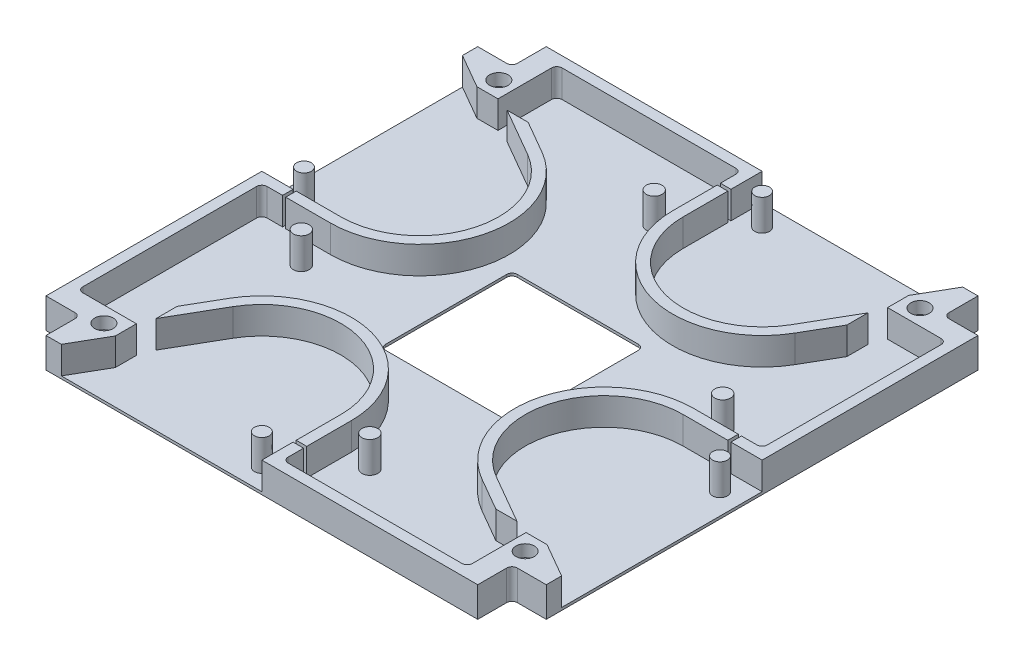
SolidWorks part; units mm, degrees
material "7075-T6 (SN)"
ref_plane "Front Plane" through (0, 0, 0) normal (0, 0, 1) x (1, 0, 0)
ref_plane "Top Plane" through (0, 0, 0) normal (0, 1, 0) x (1, 0, 0)
ref_plane "Right Plane" through (0, 0, 0) normal (1, 0, 0) x (0, 0, -1)
sketch "Sketch1" plane through (0, 0, 0) normal (0, 1, 0) x (1, 0, 0)
  line L0 (0, 0) -> (0, 6.51)
  line L21 (0, 6.51) -> (82, 6.51)
  line L22 (82, 6.51) -> (82, 0)
  line L23 (82, 0) -> (88.51, 0)
  line L24 (88.51, 0) -> (88.51, -82)
  line L25 (88.51, -82) -> (82, -82)
  line L26 (82, -82) -> (82, -88.51)
  line L27 (82, -88.51) -> (0, -88.51)
  line L28 (0, -88.51) -> (0, -82)
  line L29 (0, -82) -> (-6.51, -82)
  line L30 (-6.51, -82) -> (-6.51, 0)
  line L31 (-6.51, 0) -> (0, 0)
  dimension "D1" = 82
  dimension "D2" = 6.51
extrude "Boss-Extrude1" add sketch "Sketch1" along normal blind 0.5
sketch "Sketch2" plane through (0, 0.5, 0) normal (0, 1, 0) x (1, 0, 0)
  line L0 (-6.51, 0) -> (-6.51, -82) construction
  line L1 (0, 6.51) -> (41, 6.51)
  line L2 (0, 6.51) -> (0, 4.51)
  line L3 (0, 4.51) -> (41, 4.51)
  line L4 (41, 6.51) -> (41, 4.51)
  line L5 (88.51, 0) -> (86.51, 0)
  line L6 (88.51, 0) -> (88.51, -41)
  line L7 (88.51, -41) -> (86.51, -41)
  line L8 (86.51, 0) -> (86.51, -41)
  line L9 (82, -88.51) -> (41, -88.51)
  line L10 (82, -88.51) -> (82, -86.51)
  line L11 (82, -86.51) -> (41, -86.51)
  line L12 (41, -88.51) -> (41, -86.51)
  line L13 (-6.51, -82) -> (-4.51, -82)
  line L14 (-6.51, -82) -> (-6.51, -41)
  line L15 (-6.51, -41) -> (-4.51, -41)
  line L16 (-4.51, -82) -> (-4.51, -41)
  line L17 (-6.51, -82) -> (0, -82) construction
  line L18 (41, -8.49) -> (41, 24.5303) construction
  line L19 (56, 6.51) -> (0, 6.51) construction
  line L20 (82, 6.51) -> (0, 6.51) construction
  line L21 (79.094, 6.51) -> (75.3355, 0)
  line L22 (79.094, 6.51) -> (82, 6.51)
  line L23 (82, 6.51) -> (82, 0)
  line L24 (82, 0) -> (86.51, 0)
  line L25 (41, 4.51) -> (41, -8.49)
  line L26 (86.51, -4) -> (75.3355, -4)
  line L27 (39, 4.51) -> (39, -8.49)
  line L28 (72.9929, -8) -> (73.0261, -8)
  line L29 (74.3355, -10.7321) -> (70.7224, -16.99)
  line L31 (75.3355, -4) -> (75.3355, 0)
  line L32 (74.3355, -6.7321) -> (74.3355, -10.7321)
  line L33 (74.3355, -6.7321) -> (68.9904, -15.99)
  circle A0 centre (56, -8.49) radius 15
  circle A1 centre (56, -8.49) radius 17 construction
  arc A2 (70.7224, -16.99) -> (39, -8.49) centre (56, -8.49) cw
  line M24 (88.51, -82) -> (88.51, 0)
  line M25 (88.51, 0) -> (82, 0)
  line M26 (82, 0) -> (82, 6.51)
  line M27 (82, 6.51) -> (0, 6.51)
  line M28 (0, 6.51) -> (0, 0)
  dimension "D3" = 30
  dimension "D6" = 34
  dimension "D1" = 41
  dimension "D2" = 2
  dimension "D7" = 4
  dimension "D8" = 4
  dimension "D5" = 0
  dimension "D9" = 1
  dimension "D4" = 30
  dimension "D10" = 6.6645
  dimension "D11" = 30
  dimension "D12" = 4
extrude "Boss-Extrude2" add sketch "Sketch2" along normal blind 5.2 contours L4 L3 M27 M28 | A2 L28 A0 L25 L3 L27 | L8 L7 M25 M24 | L26 L8 M25 M26 M27 region at (80.332, 0.5, 0.0167) region at (20.5, 0.5, -5.51) region at (40.5365, 0.5, 1.99) region at (87.51, 0.5, 20.5)
sketch "Sketch3" [suppressed] plane through (0, 0.5, 0) normal (0, 1, 0) x (1, 0, 0)
  line L0 (35.5217, -6.4679) -> (39.51, -26.4679)
  line L1 (39.51, -26.4679) -> (39.51, -29.4679)
  line L2 (39.51, -29.4679) -> (79.51, -29.4679)
  line L3 (79.51, -29.4679) -> (79.51, -26.4679)
  line L4 (79.51, -26.4679) -> (83.4983, -6.4679)
  line L6 (35.5217, -6.4679) -> (39.5217, -6.4679)
  line L7 (83.4983, -6.4679) -> (79.4983, -6.4679)
  line L9 (89.51, -41) -> (89.51, 0) construction
  arc A0 (79.4983, -6.4679) -> (39.5217, -6.4679) centre (59.51, -5.7836) cw
  circle A1 centre (58.485, 0) radius 15 construction
  dimension "D3" = 20
  dimension "D7" = 30
  dimension "D1" = 3
  dimension "D2" = 4
  dimension "D4" = 20
  dimension "D5" = 40
  dimension "D6" = 10
extrude "Boss-Extrude3" [suppressed] add sketch "Sketch3" along normal blind 6
ref_plane "Plane1" through (41, 0, 41) normal (0.7071, 0, 0.7071) x (0.7071, 0, -0.7071)
ref_plane "Plane2" through (0, 0, 0) normal (0.7071, 0, -0.7071) x (-0.7071, 0, -0.7071)
ref_axis "Axis1" through (41, -0.325, 41) along (0, 1, 0)
pattern_circular "CirPattern1" count 4 every 90 about axis through (41, -0.325, 41) along (0, 1, 0) of "Boss-Extrude2"
sketch "Sketch4" plane through (0, 0, 0) normal (0, -1, 0) x (1, 0, 0)
  line L0 (78, -6.51) -> (78, -0.51) construction
  line L1 (82, -6.51) -> (0, -6.51) construction
  line L2 (82, 0) -> (82, -6.51) construction
  line L3 (88.51, 78) -> (82.51, 78) construction
  line L4 (88.51, 82) -> (88.51, 0) construction
  line L5 (4, 88.51) -> (4, 82.51) construction
  line L6 (0, 88.51) -> (82, 88.51) construction
  line L7 (-6.51, 4) -> (-0.51, 4) construction
  line L8 (-6.51, 0) -> (-6.51, 82) construction
  line L10 (82, 82) -> (88.51, 82) construction
  line L11 (0, 82) -> (0, 88.51) construction
  line L12 (0, 0) -> (-6.51, 0) construction
  point P7 (78, -0.51)
  dimension "D1" = 6
  dimension "D2" = 4
  dimension "D3" = 4
  dimension "D4" = 4
  dimension "D5" = 4
  dimension "D6" = 6
  dimension "D7" = 6
  dimension "D8" = 6
sketch "Sketch8" plane through (0, 0.5, 0) normal (0, 1, 0) x (1, 0, 0)
  line L0 (2.906, -88.51) -> (41, -88.51) construction
  line L1 (41, -88.51) -> (41, -73.51) construction
  circle A0 centre (37, -84.51) radius 1.4
  dimension "D1" = 2.8
  dimension "D2" = 4
  dimension "D3" = 4
extrude "Boss-Extrude4" add sketch "Sketch8" along normal blind 5.9
pattern_circular "CirPattern2" count 4 every 90 about axis through (41, -0.325, 41) along (0, 1, 0) of "Boss-Extrude4"
fillet "Fillet1" radius 1 8 edges at (-4.51, 3.1, 78) (-4.51, 3.1, 43) (4, 3.1, -4.51) (39, 3.1, -4.51) (86.51, 3.1, 4) (86.51, 3.1, 39) (78, 3.1, 86.51) (43, 3.1, 86.51)
sketch "Sketch11" plane through (0, 0.5, 0) normal (0, 1, 0) x (1, 0, 0)
  line L0 (53.5, -53.5) -> (53.5, -28.5)
  line L1 (53.5, -28.5) -> (28.5, -28.5)
  line L2 (28.5, -28.5) -> (28.5, -53.5)
  line L3 (28.5, -53.5) -> (53.5, -53.5)
  line L5 (79.094, 6.51) -> (41, 6.51) construction
  line L6 (-6.51, -2.906) -> (-6.51, -41) construction
  dimension "D1" = 25
  dimension "D2" = 25
  dimension "D3" = 35.01
  dimension "D4" = 35.01
extrude "Cut-Extrude2" cut sketch "Sketch11" against normal through all
sketch "Sketch14" plane through (0, 6.4, 0) normal (0, 1, 0) x (1, 0, 0)
  point P0 (37, -84.51)
sketch "Sketch15" plane through (0, 5.7, 0) normal (0, 1, 0) x (1, 0, 0)
  line L0 (82, -82) -> (88.51, -82) construction
  line L2 (78, -85.51) -> (78, -75.3355) construction
  circle A0 centre (81, -78.5) radius 0.9
  circle A1 centre (78.5, -1) radius 0.9
  circle A2 centre (1, -3.5) radius 0.9
  circle A3 centre (3.5, -81) radius 0.9
  point P0 (1, -3.5)
  point P1 (1, -3.5)
  point P2 (3.5, -81)
  point P3 (81, -78.5)
  point P4 (78.5, -1)
  point P5 (3.5, -81)
  dimension "D3" = 1.8
  dimension "D4" = 1.8
  dimension "D5" = 1.8
  dimension "D6" = 1.8
  dimension "D1" = 3.5
  dimension "D2" = 3
extrude "Cut-Extrude3" cut sketch "Sketch15" against normal through all
sketch "Sketch16" plane through (0, 5.7, 0) normal (0, 1, 0) x (1, 0, 0)
  circle A0 centre (78.5, -1) radius 1.75
  circle A1 centre (81, -78.5) radius 1.75
  circle A2 centre (3.5, -81) radius 1.75
  circle A3 centre (1, -3.5) radius 1.75
  dimension "D1" = 3.5
  dimension "D2" = 3.5
  dimension "D3" = 3.5
  dimension "D4" = 3.5
extrude "Cut-Extrude4" cut sketch "Sketch16" against normal blind 2.3
hole_wizard "CBORE for M1.6 SHCS2" positions "3DSketch2" profile "Sketch18" counterbore size "M1.6" standard "ANSI Metric" end condition through all
sketch3d "3DSketch2"
  line L0 (81, 0, 78.5) -> (81, 3.4, 78.5) construction
  line L1 (78.5, 0, 1) -> (78.5, 3.4, 1) construction
  line L2 (1, 0, 3.5) -> (1, 3.4, 3.5) construction
  line L3 (3.5, 0, 81) -> (3.5, 3.4, 81) construction
  point P0 (81, 0, 78.5)
  point P4 (78.5, 0, 1)
  point P8 (1, 0, 3.5)
  point P12 (3.5, 0, 81)
sketch "Sketch18" plane through (81, 0, 78.5) normal (1, 0, 0) x (0, 0, -1)
  line L0 (0, 0) -> (0, 6.4)
  line L1 (0, 6.4) -> (0.9, 6.4)
  line L3 (0.9, 6.4) -> (0.9, 1.6)
  line L4 (0.9, 1.6) -> (1.75, 1.6)
  line L5 (1.75, 1.6) -> (1.75, 0)
  line L7 (1.75, 0) -> (0, 0)
  line L11 (0, -6.35) -> (0, 107.95) construction
  dimension "Thru Hole Dia." = 1.8
  dimension "Thru Hole Depth" = 6.4
  dimension "C'Bore Dia." = 3.5
  dimension "C'Bore Depth" = 1.6
sketch "Sketch20" plane through (0, 5.7, 0) normal (0, 1, 0) x (1, 0, 0)
  line L0 (82.585, -39) -> (82.585, -41)
  line L1 (85.51, -39) -> (73.51, -39) construction
  line L2 (88.51, -41) -> (73.51, -41) construction
  line L3 (82.585, -41) -> (81.985, -41)
  line L4 (81.985, -41) -> (81.985, -39)
  line L5 (81.985, -39) -> (82.585, -39)
  circle A0 centre (84.51, -45) radius 1.4 construction
  dimension "D1" = 1.925
  dimension "D2" = 2.525
sketch "Sketch24" plane through (0, 0.5, 0) normal (0, 1, 0) x (1, 0, 0)
  point P0 (41, -41)
  dimension "D1" = 41
  dimension "D2" = 41
extrude "Cut-Extrude6" cut sketch "Sketch20" against normal up to surface (5.2 mm away) up to face at (41, 0.5, 41)
pattern_circular "CirPattern3" count 4 over 360 about axis through (41, -0.325, 41) along (0, 1, 0) of "Cut-Extrude6"
fillet "Fillet2" radius 1 4 edges at (0, 2.85, 0) (82, 2.85, 0) (82, 2.85, 82) (0, 2.85, 82)
sketch "Sketch25" plane through (0, 0.5, 0) normal (0, 1, 0) x (1, 0, 0)
  line L1 (79.094, 6.51) -> (41, 6.51) construction
  line L2 (88.51, -41) -> (88.51, 0) construction
  circle A0 centre (74.51, -34.49) radius 1.5
  point P0 (74.51, -34.49)
  dimension "D2" = 3
  dimension "D1" = 41
  dimension "D3" = 14
extrude "Boss-Extrude5" add sketch "Sketch25" along normal blind 5.9
pattern_circular "CirPattern4" count 4 over 360 about axis through (41, -0.325, 41) along (0, 1, 0) of "Boss-Extrude5"
fillet "Fillet3" radius 1 4 edges at (28.5, 0.25, 28.5) (28.5, 0.25, 53.5) (53.5, 0.25, 53.5) (53.5, 0.25, 28.5)
equation "\"D6@Sketch2\"=\"D3@Sketch2\"+4"
equation "\"D3@Sketch4\"=\"D2@Sketch4\""
equation "\"D4@Sketch4\"=\"D3@Sketch4\""
equation "\"D5@Sketch4\"=\"D4@Sketch4\""
equation "\"D6@Sketch4\"=\"D1@Sketch4\""
equation "\"D7@Sketch4\"=\"D6@Sketch4\""
equation "\"D8@Sketch4\"=\"D7@Sketch4\""
